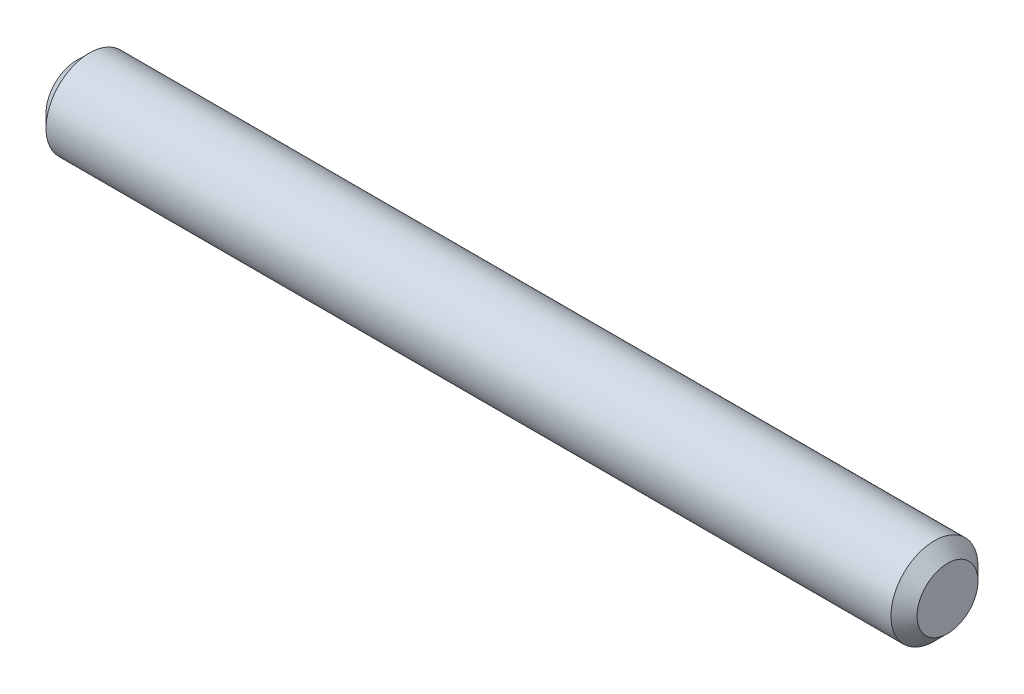
SolidWorks part; units mm, degrees
ref_plane "Front Plane" through (0, 0, 0) normal (0, 0, 1) x (1, 0, 0)
ref_plane "Top Plane" through (0, 0, 0) normal (0, 1, 0) x (1, 0, 0)
ref_plane "Right Plane" through (0, 0, 0) normal (1, 0, 0) x (0, 0, -1)
sketch "Sketch1" plane through (0, 0, 0) normal (0, 0, 1) x (1, 0, 0)
  line L0 (-31.75, 0) -> (31.75, 0) construction
  line L1 (31.75, 3.175) -> (31.75, -3.175) construction
  line L2 (-31.75, 3.175) -> (-31.75, -3.175) construction
  point P6 (27.305, -3.175)
  dimension "Thread Diameter" = 6.35
  dimension "Length" = 63.5
  dimension "D1" = 4.445
sketch "Sketch2" plane through (0, 0, 0) normal (1, 0, 0) x (0, 0, -1)
  circle A0 centre (0, 0) radius 3.175
extrude "Boss-Extrude1" add sketch "Sketch2" against normal up to vertex (31.75 mm away) and the other way up to vertex (31.75 mm away) up to point (-31.75, 0, 0) other way up to point (31.75, 0, 0)
cosmetic thread "Cosmetic Thread1" parameters "D2"=4.8387
sketch "Sketch3" plane through (31.75, 0, 0) normal (1, 0, 0) x (0, 0, -1)
  circle A1 centre (0, 0) radius 3.175
  circle A2 centre (0, 0) radius 3.175
  dimension "D1" = 0
curve "Helix/Spiral1" pitch 1.27 height 64.77 turns 51 parameters "Pitch"=1.27
chamfer "Chamfer1" distance 0.9525 angle 45 2 edges at (-31.75, 0, -3.175) (31.75, 0, -3.175)
sketch "Sketch4" plane through (0, 0, 0) normal (0, 0, 1) x (1, 0, 0)
  line L0 (31.6706, 3.3125) -> (32.3056, 2.2126) construction
  line L1 (32.3056, 2.2126) -> (32.9406, 3.3125) construction
  line L2 (32.9406, 3.3125) -> (31.6706, 3.3125) construction
  line L3 (32.3056, 3.3125) -> (32.3056, 3.175) construction
  line L4 (32.3056, 2.2126) -> (32.3056, 2.3501) construction
  line L5 (32.2263, 2.3501) -> (32.385, 2.3501) construction
  line L6 (31.75, 3.175) -> (32.8613, 3.175) construction
  line L7 (32.2263, 2.3501) -> (31.7103, 3.2437)
  line L8 (32.2263, 2.3501) -> (32.385, 2.3501)
  line L9 (31.7103, 3.2437) -> (32.9009, 3.2437)
  line L10 (32.9009, 3.2437) -> (32.385, 2.3501)
  point P13 (32.3056, 3.2437)
  dimension "D2" = 0.1588
sweep "Cut-Sweep3" [suppressed] cut profiles "Sketch4" path "Helix/Spiral1"
equation "\"D3@Helix/Spiral1\" = \"Length@Sketch1\"+\"Pitch@Helix/Spiral1\""
equation "\"D1@Chamfer1\" = \"Pitch@Helix/Spiral1\"*.75"
equation "\"D1@Sketch4\" = \"Pitch@Helix/Spiral1\""
equation "\"D2@Sketch4\" = \"D1@Sketch4\"/8"
equation "\"D1@Sketch1\" = \"Pitch@Helix/Spiral1\"*3.50"
